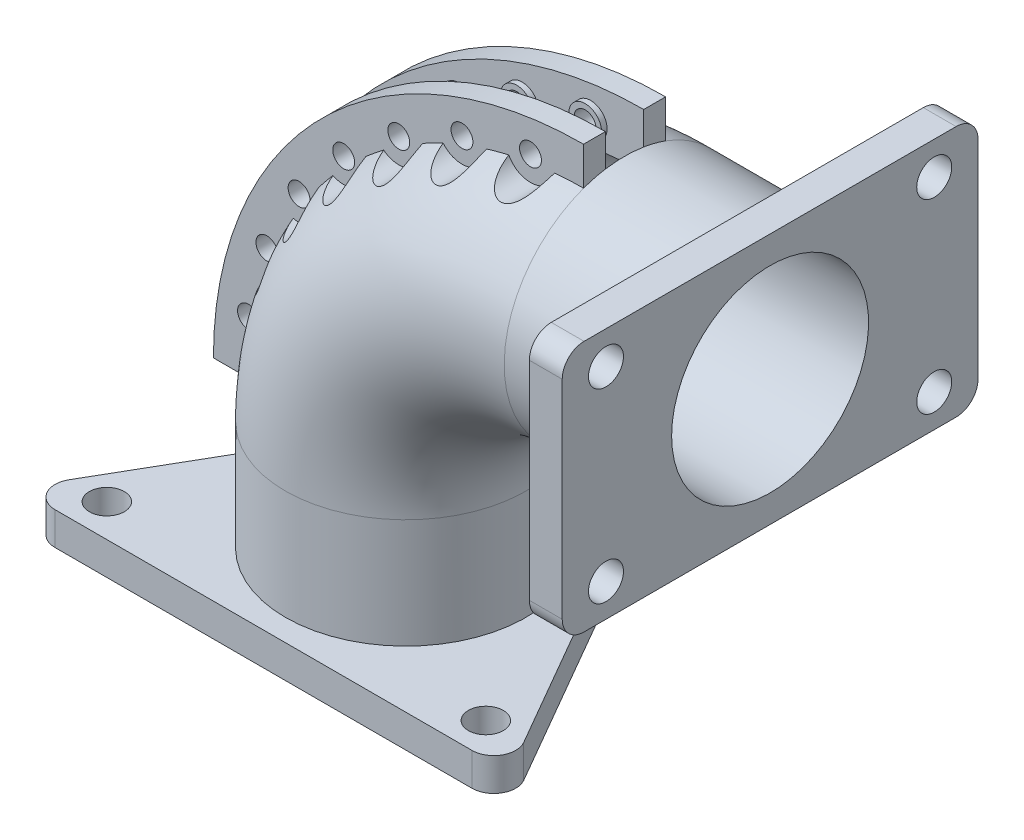
SolidWorks part; units mm, degrees
material "聚脂树脂"
ref_plane "前视基准面" through (0, 0, 0) normal (0, 0, 1) x (1, 0, 0)
ref_plane "上视基准面" through (0, 0, 0) normal (0, 1, 0) x (1, 0, 0)
ref_plane "右视基准面" through (0, 0, 0) normal (1, 0, 0) x (0, 0, -1)
sketch "草图1" plane through (0, 0, 0) normal (0, 1, 0) x (1, 0, 0)
  line L0 (0, 40) -> (0, 0) construction
  line L4 (0, 0) -> (-34.641, -20) construction
  line L5 (0, 0) -> (34.641, -20) construction
  line L6 (-1.7321, 23) -> (-20.7846, -10)
  line L7 (-19.0526, -13) -> (19.0526, -13)
  line L8 (20.7846, -10) -> (1.7321, 23)
  circle A0 centre (0, 0) radius 9
  circle A2 centre (0, 0) radius 20 construction
  circle A3 centre (0, 20) radius 1.6
  circle A4 centre (-17.3205, -10) radius 1.6
  circle A5 centre (17.3205, -10) radius 1.6
  arc A9 (-1.7321, 23) -> (1.7321, 23) centre (0, 22) cw
  arc A10 (19.0526, -13) -> (20.7846, -10) centre (19.0526, -11) ccw
  arc A11 (-20.7846, -10) -> (-19.0526, -13) centre (-19.0526, -11) ccw
  point P18 (0, 26)
  point P21 (22.5167, -13)
  point P24 (-22.5167, -13)
  dimension "D1" = 18
  dimension "D2" = 40
  dimension "D3" = 3.2
  dimension "D4" = 120
  dimension "D5" = 3.2
  dimension "D6" = 120
  dimension "D7" = 3.2
  dimension "D8" = 26
  dimension "D10" = 2
  dimension "D9" = 26
extrude "凸台-拉伸1" add sketch "草图1" along normal blind 3
sketch "草图2" plane through (0, 3, 0) normal (0, 1, 0) x (1, 0, 0)
  circle A0 centre (0, 0) radius 9
  circle A1 centre (0, 0) radius 11
  dimension "D1" = 22
  dimension "D2" = 18
sketch "草图3" plane through (0, 0, 0) normal (0, 0, 1) x (1, 0, 0)
  line L0 (0, 3) -> (0, 13)
  line L1 (11, 3) -> (-11, 3) construction
  line L2 (20, 33) -> (20, 13) construction
  line L3 (20, 33) -> (33.3, 33)
  arc A0 (0, 13) -> (20, 33) centre (20, 13) cw
  dimension "D1" = 10
  dimension "D2" = 20
  dimension "D3" = 13.3
sweep "扫描1" add profiles "草图2" path "草图3"
sketch "草图4" plane through (33.3, 0, 0) normal (1, 0, 0) x (0, 0, -1)
  line L0 (0, 33) -> (0, 37.8313) construction
  line L1 (17, 21.5) -> (-17, 21.5)
  line L2 (19, 23.5) -> (19, 42.5)
  line L3 (17, 44.5) -> (-17, 44.5)
  line L4 (-19, 23.5) -> (-19, 42.5)
  line L5 (19, 21.5) -> (-19, 44.5) construction
  line L6 (19, 44.5) -> (-19, 21.5) construction
  line L7 (0, 33) -> (4.7838, 33) construction
  circle A0 centre (0, 33) radius 9
  circle A1 centre (-15, 41.5) radius 1.6
  circle A2 centre (15, 41.5) radius 1.6
  circle A3 centre (-15, 24.5) radius 1.6
  circle A4 centre (15, 24.5) radius 1.6
  arc A5 (19, 42.5) -> (17, 44.5) centre (17, 42.5) ccw
  arc A6 (17, 21.5) -> (19, 23.5) centre (17, 23.5) ccw
  arc A7 (-17, 21.5) -> (-19, 23.5) centre (-17, 23.5) cw
  arc A8 (-17, 44.5) -> (-19, 42.5) centre (-17, 42.5) ccw
  dimension "D1" = 18
  dimension "D4" = 3.2
  dimension "D7" = 2
  dimension "D2" = 38
  dimension "D3" = 23
  dimension "D5" = 8.5
  dimension "D6" = 15
extrude "凸台-拉伸3" add sketch "草图4" against normal blind 3
sketch "草图5" plane through (0, 0, 0) normal (0, 0, 1) x (1, 0, 0)
  line L0 (-11, 13) -> (-11, 3) construction
  line L4 (11, 13) -> (-11, 13) construction
  line L5 (20, 22) -> (20, 44) construction
  line L6 (30.3, 44) -> (20, 44) construction
  line L7 (-8, 13) -> (-14.303, 13)
  line L8 (20, 47.0087) -> (20, 41)
  arc A0 (-8, 13) -> (20, 41) centre (20, 13) cw
  arc A1 (-14.303, 13) -> (20, 47.0087) centre (19.7069, 13) cw
  dimension "D1" = 3
  dimension "D2" = 3
extrude "切除-拉伸1" cut sketch "草图5" against normal blind 1.75 and the other way blind 1.75
sketch "草图6" plane through (0, 0, -1.75) normal (0, 0, 1) x (1, 0, 0)
  line L0 (20, 41.8282) -> (20, 46.8282)
  line L1 (-13.8282, 13) -> (-8.8282, 13)
  arc A0 (20, 41.8282) -> (-8.8282, 13) centre (20, 13) ccw construction
  arc A1 (20, 41.8282) -> (-8.8282, 13) centre (20, 13) ccw
  arc A2 (20, 46.8282) -> (-13.8282, 13) centre (20, 13) ccw
  dimension "D1" = 5
  dimension "D2" = 5
extrude "凸台-拉伸4" add sketch "草图6" against normal blind 2
sketch "草图7" plane through (0, 0, 1.75) normal (0, 0, -1) x (-1, 0, 0)
  line L0 (-20, 41.8282) -> (-20, 46.8282)
  line L1 (13.8282, 13) -> (8.8282, 13)
  arc A0 (8.8282, 13) -> (-20, 41.8282) centre (-20, 13) ccw construction
  arc A1 (8.8282, 13) -> (-20, 41.8282) centre (-20, 13) ccw
  arc A2 (-20, 46.8282) -> (13.8282, 13) centre (-20, 13) cw
  dimension "D1" = 5
  dimension "D2" = 5
extrude "凸台-拉伸5" add sketch "草图7" against normal blind 2
sketch "草图8" plane through (0, 0, 3.75) normal (0, 0, 1) x (1, 0, 0)
  line L0 (20, 44) -> (20, 9.0901) construction
  line L1 (-10.8599, 13) -> (20, 13) construction
  line L2 (20, 13) -> (15.1505, 43.6183) construction
  line L3 (8.8906, 41.941) -> (20, 13) construction
  line L4 (20, 13) -> (8.8906, 41.941) construction
  line L5 (20, 13) -> (3.1162, 38.9988) construction
  circle A0 centre (20, 13) radius 31 construction
  circle A1 centre (15.1505, 43.6183) radius 1
  circle A2 centre (15.1505, 43.6183) radius 2.5 construction
  circle A3 centre (8.8906, 41.941) radius 1
  circle A4 centre (8.8906, 41.941) radius 2.5 construction
  circle A5 centre (3.1162, 38.9988) radius 1
  circle A6 centre (-1.9203, 34.9203) radius 1
  circle A7 centre (-5.9988, 29.8838) radius 1
  circle A8 centre (-8.941, 24.1094) radius 1
  circle A9 centre (-10.6183, 17.8495) radius 1
  dimension "D1" = 2
  dimension "D2" = 5
  dimension "D3" = 2
  dimension "D4" = 5
  dimension "D5" = 12
  dimension "D6" = 9
  dimension "D8" = 12
  dimension "D7" = 6
extrude "切除-拉伸2" cut sketch "草图8" against normal through all both and the other way through all
sketch "草图9" plane through (0, 0, 3.75) normal (0, 0, 1) x (1, 0, 0)
  circle A0 centre (15.1505, 43.6183) radius 2.25
  circle A1 centre (8.8906, 41.941) radius 2.25
  circle A2 centre (3.1162, 38.9988) radius 2.25
  circle A3 centre (-1.9203, 34.9203) radius 2.25
  circle A4 centre (-5.9988, 29.8838) radius 2.25
  circle A5 centre (-8.941, 24.1094) radius 2.25
  circle A6 centre (-10.6183, 17.8495) radius 2.25
  dimension "D1" = 4.5
  dimension "D2" = 4.5
  dimension "D3" = 4.5
  dimension "D4" = 4.5
  dimension "D5" = 4.5
  dimension "D6" = 4.5
  dimension "D7" = 4.5
extrude "切除-拉伸3" cut sketch "草图9" along normal through all
sketch "草图10" plane through (0, 0, -3.75) normal (0, 0, -1) x (-1, 0, 0)
  circle A1 centre (5.9988, 29.8838) radius 2.25
  circle A2 centre (5.9988, 29.8838) radius 2.25
  circle A3 centre (1.9203, 34.9203) radius 2.25
  circle A4 centre (1.9203, 34.9203) radius 2.25
  circle A5 centre (-3.1162, 38.9988) radius 2.25
  circle A6 centre (-3.1162, 38.9988) radius 2.25
  circle A7 centre (-8.8906, 41.941) radius 2.25
  circle A8 centre (-8.8906, 41.941) radius 2.25
  circle A9 centre (-15.1505, 43.6183) radius 2.25
  circle A10 centre (-15.1505, 43.6183) radius 2.25
  circle A11 centre (10.6183, 17.8495) radius 2.25
  circle A12 centre (10.6183, 17.8495) radius 2.25
  circle A13 centre (8.941, 24.1094) radius 2.25
  circle A14 centre (8.941, 24.1094) radius 2.25
  dimension "D1" = 0
  dimension "D2" = 0
  dimension "D3" = 0
  dimension "D4" = 0
  dimension "D5" = 0
  dimension "D6" = 0
  dimension "D7" = 0
extrude "切除-拉伸4" cut sketch "草图10" along normal through all
sketch "草图11" plane through (0, 0, -1.75) normal (0, 0, 1) x (1, 0, 0)
  circle A0 centre (15.1505, 43.6183) radius 1
  circle A1 centre (15.1505, 43.6183) radius 1.5
  circle A2 centre (8.8906, 41.941) radius 1
  circle A3 centre (8.8906, 41.941) radius 1.5
  circle A4 centre (3.1162, 38.9988) radius 1
  circle A5 centre (3.1162, 38.9988) radius 1.5
  circle A6 centre (-1.9203, 34.9203) radius 1
  circle A7 centre (-1.9203, 34.9203) radius 1.5
  circle A8 centre (-5.9988, 29.8838) radius 1
  circle A9 centre (-5.9988, 29.8838) radius 1.5
  circle A10 centre (-8.941, 24.1094) radius 1
  circle A11 centre (-8.941, 24.1094) radius 1.5
  circle A12 centre (-10.6183, 17.8495) radius 1
  circle A13 centre (-10.6183, 17.8495) radius 1.5
  dimension "D1" = 2
  dimension "D2" = 3
  dimension "D3" = 2
  dimension "D4" = 3
  dimension "D5" = 2
  dimension "D6" = 3
  dimension "D7" = 3
  dimension "D8" = 2
  dimension "D9" = 2
  dimension "D10" = 3
  dimension "D11" = 3
  dimension "D12" = 2
  dimension "D13" = 2
  dimension "D14" = 3
extrude "凸台-拉伸6" add sketch "草图11" along normal blind 0.5
sketch "草图12" plane through (0, 0, 1.75) normal (0, 0, -1) x (-1, 0, 0)
  circle A1 centre (1.9203, 34.9203) radius 1.5
  circle A2 centre (1.9203, 34.9203) radius 1.5
  circle A3 centre (1.9203, 34.9203) radius 1
  circle A4 centre (1.9203, 34.9203) radius 1
  circle A5 centre (-3.1162, 38.9988) radius 1.5
  circle A6 centre (-3.1162, 38.9988) radius 1.5
  circle A7 centre (-3.1162, 38.9988) radius 1
  circle A8 centre (-3.1162, 38.9988) radius 1
  circle A9 centre (-8.8906, 41.941) radius 1.5
  circle A10 centre (-8.8906, 41.941) radius 1.5
  circle A11 centre (-8.8906, 41.941) radius 1
  circle A12 centre (-8.8906, 41.941) radius 1
  circle A13 centre (-15.1505, 43.6183) radius 1.5
  circle A14 centre (-15.1505, 43.6183) radius 1.5
  circle A15 centre (-15.1505, 43.6183) radius 1
  circle A16 centre (-15.1505, 43.6183) radius 1
  circle A17 centre (10.6183, 17.8495) radius 1.5
  circle A18 centre (10.6183, 17.8495) radius 1.5
  circle A19 centre (10.6183, 17.8495) radius 1
  circle A20 centre (10.6183, 17.8495) radius 1
  circle A21 centre (8.941, 24.1094) radius 1.5
  circle A22 centre (8.941, 24.1094) radius 1.5
  circle A23 centre (8.941, 24.1094) radius 1
  circle A24 centre (8.941, 24.1094) radius 1
  circle A25 centre (5.9988, 29.8838) radius 1.5
  circle A26 centre (5.9988, 29.8838) radius 1.5
  circle A27 centre (5.9988, 29.8838) radius 1
  circle A28 centre (5.9988, 29.8838) radius 1
  dimension "D1" = 0
  dimension "D2" = 0
  dimension "D3" = 0
  dimension "D4" = 0
  dimension "D5" = 0
  dimension "D6" = 0
  dimension "D7" = 0
  dimension "D8" = 0
  dimension "D9" = 0
  dimension "D10" = 0
  dimension "D11" = 0
  dimension "D12" = 0
  dimension "D13" = 0
  dimension "D14" = 0
extrude "凸台-拉伸7" add sketch "草图12" along normal blind 0.5
